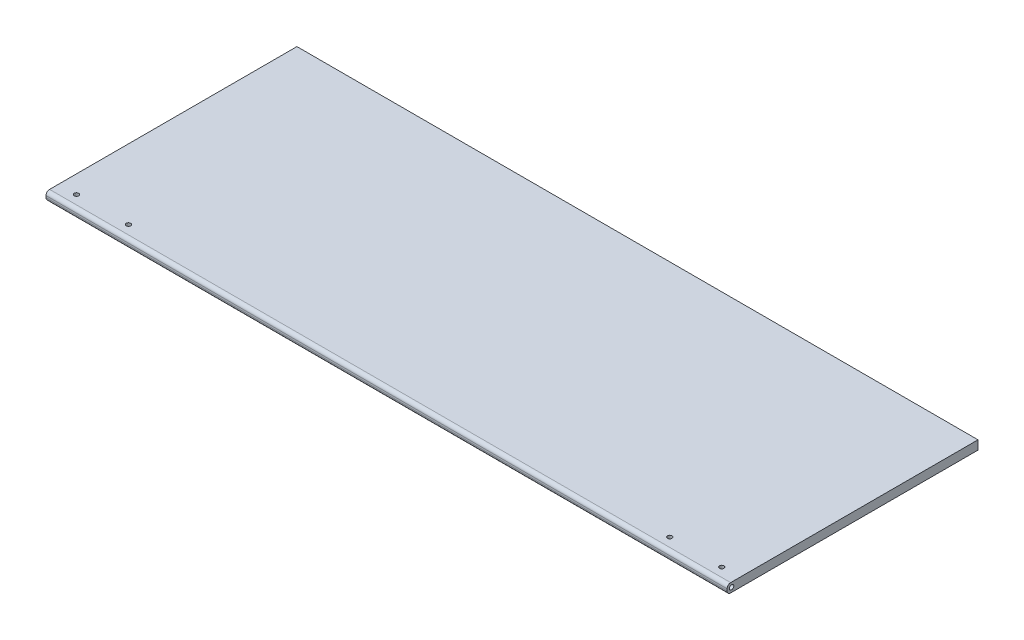
SolidWorks part; units mm, degrees
material "6061 Alloy"
ref_plane "Front Plane" through (0, 0, 0) normal (0, 0, 1) x (1, 0, 0)
ref_plane "Top Plane" through (0, 0, 0) normal (0, 1, 0) x (1, 0, 0)
ref_plane "Right Plane" through (0, 0, 0) normal (1, 0, 0) x (0, 0, -1)
sketch "Sketch1" plane through (0, 0, 0) normal (0, 1, 0) x (1, 0, 0)
  line L1 (-241.3, 88.9) -> (241.3, 88.9)
  line L2 (-241.3, 88.9) -> (-241.3, -88.9)
  line L3 (-241.3, -88.9) -> (241.3, -88.9)
  line L4 (241.3, 88.9) -> (241.3, -88.9)
  line L5 (-241.3, 88.9) -> (241.3, -88.9) construction
  line L6 (-241.3, -88.9) -> (241.3, 88.9) construction
  point P0 (0, 0)
  dimension "D1" = 177.8
  dimension "D2" = 482.6
extrude "Boss-Extrude1" add sketch "Sketch1" along normal blind 6.35
sketch "Sketch2" plane through (-241.3, 0, 0) normal (-1, 0, 0) x (0, 0, 1)
  line L0 (-88.9, 6.35) -> (88.9, 6.35) construction
  line L1 (88.9, 6.35) -> (88.9, 0) construction
  circle A0 centre (85.725, 3.175) radius 1.5875
  dimension "D1" = 3.175
  dimension "D2" = 3.175
  dimension "D3" = 3.175
extrude "Cut-Extrude1" cut sketch "Sketch2" against normal through all
fillet "Fillet1" radius 2.54 2 edges at (0, 0, 88.9) (0, 6.35, 88.9)
sketch "Sketch3" plane through (241.3, 0, 0) normal (1, 0, 0) x (0, 0, -1)
  line L0 (88.9, 6.35) -> (88.9, 0) construction
  line L1 (-48.26, 4.572) -> (-33.02, 4.572)
  line L2 (-48.26, 4.572) -> (-48.26, 1.27)
  line L3 (-48.26, 1.27) -> (-33.02, 1.27)
  line L4 (-33.02, 4.572) -> (-33.02, 1.27)
  line L5 (-48.26, 4.572) -> (-33.02, 1.27) construction
  line L6 (-48.26, 1.27) -> (-33.02, 4.572) construction
  line L7 (-86.36, 0) -> (88.9, 0) construction
  point P0 (-40.64, 2.921)
  dimension "D1" = 15.24
  dimension "D2" = 129.54
  dimension "D3" = 3.302
  dimension "D4" = 1.27
sketch "Sketch4" plane through (0, 0, 0) normal (0, -1, 0) x (1, 0, 0)
  line L0 (241.3, 86.36) -> (-241.3, 86.36) construction
  line L1 (-241.3, -88.9) -> (-241.3, 86.36) construction
  circle A0 centre (-191.77, 80.01) radius 1.5875
  circle A1 centre (-228.6, 80.01) radius 1.5875
  dimension "D2" = 3.175
  dimension "D1" = 6.35
  dimension "D3" = 36.83
  dimension "D4" = 12.7
extrude "Cut-Extrude3" cut sketch "Sketch4" against normal through all
mirror "Mirror1" about plane through (0, 0, 0) normal (1, 0, 0) of "Cut-Extrude3"
